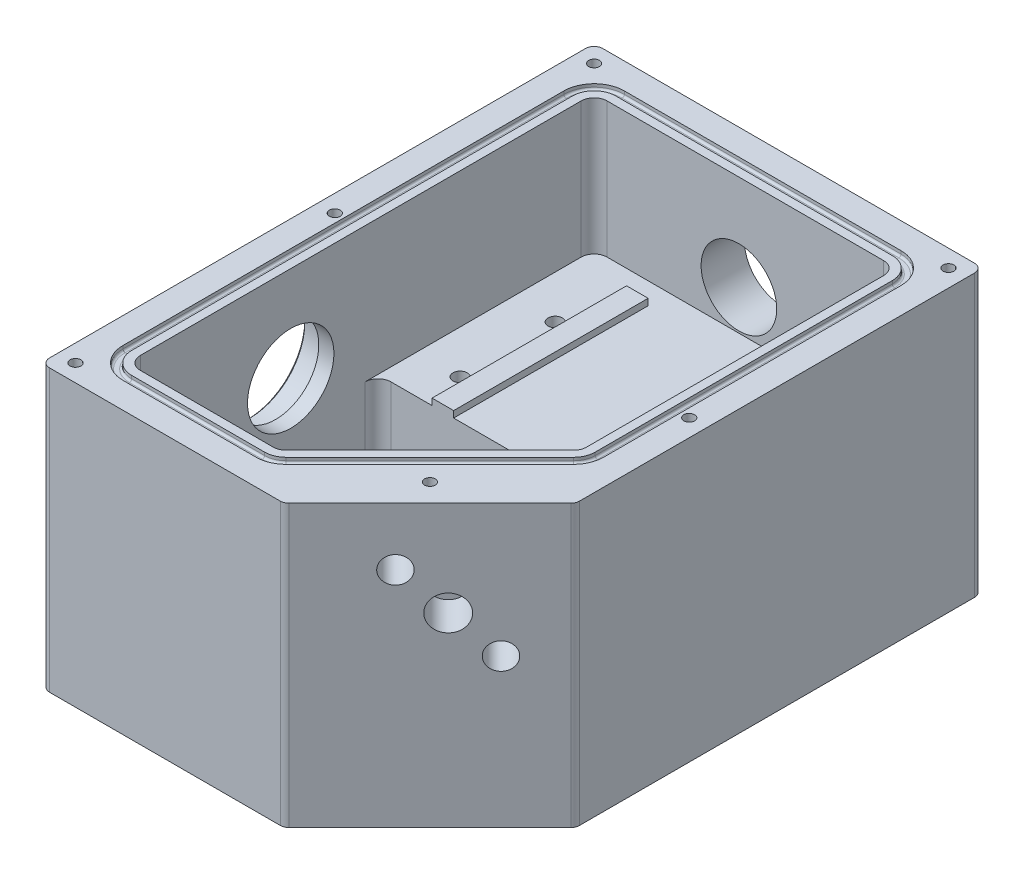
SolidWorks part; units mm, degrees
ref_plane "Front Plane" through (0, 0, 0) normal (0, 0, 1) x (1, 0, 0)
ref_plane "Top Plane" through (0, 0, 0) normal (0, 1, 0) x (1, 0, 0)
ref_plane "Right Plane" through (0, 0, 0) normal (1, 0, 0) x (0, 0, -1)
sketch "Sketch1" plane through (0, 0, 0) normal (0, 1, 0) x (1, 0, 0)
  line L1 (-45, -59) -> (45, -59)
  line L2 (-45, -59) -> (-45, 59)
  line L3 (-45, 59) -> (45, 59)
  line L4 (45, -59) -> (45, 59)
  line L5 (-45, -59) -> (45, 59) construction
  line L6 (-45, 59) -> (45, -59) construction
  point P0 (0, 0)
  dimension "D1" = 118
  dimension "D2" = 90
extrude "Boss-Extrude1" add sketch "Sketch1" along normal blind 15
sketch "Sketch3" plane through (0, 15, 0) normal (0, 1, 0) x (1, 0, 0)
  line L0 (45, -59) -> (45, 59) construction
  line L1 (-45, 59) -> (45, 59)
  line L2 (-45, 59) -> (-45, 9)
  line L3 (-45, 9) -> (45, 9)
  line L4 (45, 59) -> (45, 9)
  dimension "D1" = 50
extrude "Boss-Extrude3" add sketch "Sketch3" along normal blind 18.7
sketch "Sketch45" plane through (0, 0, -9) normal (0, 0, 1) x (1, 0, 0)
  line L1 (-22.5, 35.2) -> (-17.5, 35.2)
  line L2 (-22.5, 35.2) -> (-22.5, 33.7)
  line L3 (-22.5, 33.7) -> (-17.5, 33.7)
  line L4 (-17.5, 35.2) -> (-17.5, 33.7)
extrude "Boss-Extrude10" add sketch "Sketch45" against normal blind 45
sketch "Sketch6" plane through (0, 33.7, 0) normal (0, 1, 0) x (1, 0, 0)
  line L1 (-25, 18) -> (25, 18) construction
  line L2 (-25, 18) -> (-25, 40) construction
  line L3 (-25, 40) -> (25, 40) construction
  line L4 (25, 18) -> (25, 40) construction
  line L5 (-25, 18) -> (25, 40) construction
  line L6 (-25, 40) -> (25, 18) construction
  line L7 (-45, 9) -> (-22.5, 9) construction
  line L8 (-25, 22.18) -> (-25, 35.82) construction
  point P0 (0, 29)
  dimension "D1" = 22
  dimension "D3" = 20
hole_wizard "M4 Tapped Hole1" positions "3DSketch3" profile "Sketch7" tap size "M4" standard "ISO"
sketch3d "3DSketch3"
  point P0 (-25, 33.7, -40)
  point P3 (25, 33.7, -40)
  point P6 (25, 33.7, -18)
  point P9 (-25, 33.7, -18)
sketch "Sketch7" plane through (-25, 33.7, -40) normal (1, 0, 0) x (0, 0, 1)
  line L0 (0, 0) -> (0, 7.5954)
  line L1 (0, 7.5954) -> (1.65, 6.604)
  line L2 (1.65, 6.604) -> (1.65, 0)
  line L5 (1.65, 0) -> (0, 0)
  line L10 (0, 7.5954) -> (-1.65, 6.604) construction
  line L11 (0, -6.35) -> (0, 107.95) construction
  dimension "Tap Drill Dia." = 3.3
  dimension "Tap Drill Depth" = 6.604
  dimension "Drill Angle" = 118
cosmetic thread "Hole Thread1" parameters "D1"=3.048, "D2"=4
cosmetic thread "Hole Thread2" parameters "D1"=3.048, "D2"=4
cosmetic thread "Hole Thread3" parameters "D1"=3.048, "D2"=4
cosmetic thread "Hole Thread4" parameters "D1"=3.048, "D2"=4
sketch "Sketch9" plane through (0, 15, 0) normal (0, 1, 0) x (1, 0, 0)
  line L0 (45, -4) -> (-10, -59)
  line L1 (45, -59) -> (45, 9) construction
  line L2 (-45, -59) -> (45, -59) construction
  line L3 (-10, -59) -> (45, -59)
  line L4 (45, -59) -> (45, -4)
  dimension "D1" = 45
  dimension "D2" = 55
extrude "Boss-Extrude5" add sketch "Sketch9" along normal blind 50
sketch "Sketch10" plane through (0, 65, 0) normal (0, 1, 0) x (1, 0, 0)
  line L0 (45, -25.2132) -> (11.2132, -59)
  line L1 (45, -59) -> (45, -4) construction
  line L2 (-10, -59) -> (45, -59) construction
  line L3 (45, -4) -> (-10, -59) construction
  line L4 (11.2132, -59) -> (45, -59)
  line L5 (45, -59) -> (45, -25.2132)
  dimension "D1" = 15
extrude "Cut-Extrude2" cut sketch "Sketch10" against normal through all
ref_plane "Plane8" through (-7, 0, 7) normal (-0.7071, 0, 0.7071) x (0.7071, 0, 0.7071)
sketch "Sketch19" plane through (45, 0, 0) normal (1, 0, 0) x (0, 0, -1)
  line L1 (-25.2132, 65) -> (59, 65)
  line L2 (-25.2132, 65) -> (-25.2132, 0)
  line L3 (-25.2132, 0) -> (59, 0)
  line L4 (59, 65) -> (59, 0)
extrude "Boss-Extrude6" add sketch "Sketch19" against normal blind 10
sketch "Sketch20" plane through (0, 0, 59) normal (0, 0, 1) x (1, 0, 0)
  line L1 (11.2132, 65) -> (-45, 65)
  line L2 (11.2132, 65) -> (11.2132, 0)
  line L3 (11.2132, 0) -> (-45, 0)
  line L4 (-45, 65) -> (-45, 0)
extrude "Boss-Extrude7" add sketch "Sketch20" against normal blind 10
sketch "Sketch21" plane through (-45, 0, 0) normal (-1, 0, 0) x (0, 0, 1)
  line L1 (-59, 0) -> (59, 0)
  line L2 (-59, 0) -> (-59, 65)
  line L3 (-59, 65) -> (59, 65)
  line L4 (59, 0) -> (59, 65)
extrude "Boss-Extrude8" add sketch "Sketch21" against normal blind 10
sketch "Sketch22" plane through (0, 0, -59) normal (0, 0, -1) x (-1, 0, 0)
  line L1 (-45, 0) -> (45, 0)
  line L2 (-45, 0) -> (-45, 65)
  line L3 (-45, 65) -> (45, 65)
  line L4 (45, 0) -> (45, 65)
extrude "Boss-Extrude9" add sketch "Sketch22" along normal blind 10
fillet "Fillet1" radius 3 5 edges at (0, 40, 49) (35, 40, 14) (-35, 40, 49)
fillet "Fillet3" radius 3 2 edges at (35, 24.35, -9) (-35, 24.35, -9)
fillet "Fillet5" radius 2 5 edges at (-45, 32.5, 59) (11.2132, 32.5, 59) (-45, 32.5, -69) (45, 32.5, -69) (45, 32.5, 25.2132)
hole_wizard "CBORE for M5 Hex Head Bolt1" positions "3DSketch11" profile "Sketch49" counterbore size "M5" standard "ISO" end condition up to next
sketch3d "3DSketch11"
  line L0 (1.85, 43, 11.1991) -> (-68.0499, 43, 11.1991) construction
  point P0 (-45, 43, 11.1991)
sketch "Sketch49" plane through (-45, 43, 11.1991) normal (0, 1, 0) x (0, 0, 1)
  line L0 (0, 0) -> (0, 10)
  line L1 (0, 10) -> (10, 10)
  line L3 (10, 10) -> (10, 6.5)
  line L4 (10, 6.5) -> (12.75, 6.5)
  line L5 (12.75, 6.5) -> (12.75, 0)
  line L7 (12.75, 0) -> (0, 0)
  line L11 (0, -6.35) -> (0, 107.95) construction
  dimension "Thru Hole Dia." = 20
  dimension "Thru Hole Depth" = 10
  dimension "C'Bore Dia." = 25.5
  dimension "C'Bore Depth" = 6.5
chamfer "Chamfer1" distance 0.5 angle 45 1 edges at (-45, 43, 23.9491)
sketch "Sketch52" plane through (0, 65, 0) normal (0, 1, 0) x (1, 0, 0)
  line L16 (3, -50.2426) -> (36.2426, -17)
  line L17 (-32, -52) -> (-1.2426, -52)
  line L18 (-38, 56) -> (-38, -46)
  line L19 (32, 62) -> (-32, 62)
  line L20 (38, -12.7574) -> (38, 56)
  line L21 (3, -50.2426) -> (36.2426, -17)
  line L22 (-32, -52) -> (-1.2426, -52)
  line L23 (-38, 56) -> (-38, -46)
  line L24 (32, 62) -> (-32, 62)
  line L25 (38, -12.7574) -> (38, 56)
  arc A15 (-1.2426, -52) -> (3, -50.2426) centre (-1.2426, -46) ccw
  arc A16 (-38, -46) -> (-32, -52) centre (-32, -46) ccw
  arc A17 (-32, 62) -> (-38, 56) centre (-32, 56) ccw
  arc A18 (38, 56) -> (32, 62) centre (32, 56) ccw
  arc A19 (36.2426, -17) -> (38, -12.7574) centre (32, -12.7574) ccw
  arc A20 (-1.2426, -52) -> (3, -50.2426) centre (-1.2426, -46) ccw
  arc A21 (-38, -46) -> (-32, -52) centre (-32, -46) ccw
  arc A22 (-32, 62) -> (-38, 56) centre (-32, 56) ccw
  arc A23 (38, 56) -> (32, 62) centre (32, 56) ccw
  arc A24 (36.2426, -17) -> (38, -12.7574) centre (32, -12.7574) ccw
  dimension "D1" = 3
ref_plane "Plane29" through (0, 0, -56) normal (0, 0, -1) x (-1, 0, 0)
sketch "Sketch53" plane through (0, 0, -56) normal (0, 0, -1) x (-1, 0, 0)
  line L1 (-38.5, 63.8) -> (-37.5, 63.8)
  line L2 (-39, 64.3) -> (-39, 66.2)
  line L3 (-39, 66.2) -> (-37, 66.2)
  line L4 (-37, 64.3) -> (-37, 66.2)
  line L5 (-39, 63.8) -> (-37, 66.2) construction
  line L6 (-39, 66.2) -> (-37, 63.8) construction
  arc A0 (-37, 64.3) -> (-37.5, 63.8) centre (-37.5, 64.3) cw
  arc A1 (-38.5, 63.8) -> (-39, 64.3) centre (-38.5, 64.3) cw
  point P0 (-38, 65)
  dimension "D3" = 0.5
  dimension "D1" = 2
  dimension "D2" = 1.2
sweep "Cut-Sweep5" cut profiles "Sketch53" path "Sketch52"
mirror "Mirror2" about plane through (0, 0, 0) normal (1, 0, 0) of "Boss-Extrude10"
hole_wizard "M20 Tapped Hole1" positions "3DSketch9" profile "Sketch46" tap size "M20" standard "ISO" end condition up to next
sketch3d "3DSketch9"
  line L0 (-1.5, 42.9, -29.8) -> (-1.5, 42.9, -80.5766) construction
  point P0 (-1.5, 42.9, -69)
sketch "Sketch46" plane through (-1.5, 42.9, -69) normal (1, 0, 0) x (0, 1, 0)
  line L0 (0, 0) -> (0, 10)
  line L1 (0, 10) -> (8.75, 10)
  line L2 (8.75, 10) -> (8.75, 0)
  line L5 (8.75, 0) -> (0, 0)
  line L11 (0, -6.35) -> (0, 107.95) construction
  dimension "Thru Tap Drill Dia." = 17.5
  dimension "Thru Tap Drill Depth" = 10
cosmetic thread "Hole Thread19" parameters "D2"=20
sketch "Sketch47" plane through (0, 65, 0) normal (0, 1, 0) x (1, 0, 0)
  line L0 (-45, 5) -> (45, 5) construction
  line L1 (-45, 67) -> (-45, -57) construction
  line L2 (45, -24.3848) -> (45, 67) construction
  line L3 (0, 69) -> (0, -59) construction
  line L4 (-43, 69) -> (43, 69) construction
  line L5 (-43, -59) -> (10.3848, -59) construction
  line L6 (28.1066, -42.1066) -> (17.5, -31.5) construction
  line L7 (44.4142, -25.799) -> (11.799, -58.4142) construction
  line L8 (34.1213, -14.8787) -> (0.8787, -48.1213) construction
  point P0 (-41, 65)
  point P1 (41, 65)
  point P2 (41, 5)
  point P3 (-41, 5)
  point P4 (-41, -55)
  point P6 (23.864, -37.864)
  dimension "D1" = 4
  dimension "D2" = 4
  dimension "D3" = 4
  dimension "D4" = 6
  dimension "D5" = 4
hole_wizard "M3 Tapped Hole1" positions "3DSketch10" profile "Sketch48" tap size "M3" standard "ISO"
sketch3d "3DSketch10"
  point P0 (-41, 65, -65)
  point P3 (41, 65, -65)
  point P6 (41, 65, -5)
  point P9 (-41, 65, -5)
  point P12 (-41, 65, 55)
  point P18 (23.864, 65, 37.864)
sketch "Sketch48" plane through (-41, 65, -65) normal (1, 0, 0) x (0, 0, 1)
  line L0 (0, 0) -> (0, 9.2511)
  line L1 (0, 9.2511) -> (1.25, 8.5)
  line L2 (1.25, 8.5) -> (1.25, 0)
  line L5 (1.25, 0) -> (0, 0)
  line L10 (0, 9.2511) -> (-1.25, 8.5) construction
  line L11 (0, -6.35) -> (0, 107.95) construction
  dimension "Tap Drill Dia." = 2.5
  dimension "Tap Drill Depth" = 8.5
  dimension "Drill Angle" = 118
cosmetic thread "Hole Thread21" parameters "D1"=6, "D2"=3
cosmetic thread "Hole Thread23" parameters "D1"=6, "D2"=3
cosmetic thread "Hole Thread24" parameters "D1"=6, "D2"=3
cosmetic thread "Hole Thread25" parameters "D1"=6, "D2"=3
cosmetic thread "Hole Thread26" parameters "D1"=6, "D2"=3
cosmetic thread "Hole Thread27" parameters "D1"=6, "D2"=3
hole_wizard "Ø3.0 (3) Diameter Hole1" positions "3DSketch12" profile "Sketch56" hole size "Ø3.0" standard "ISO"
sketch3d "3DSketch12"
  line L0 (-23.15, 10, -7.5) -> (-23.15, 50, -7.5) construction
  line L1 (26.85, 50, -7.5) -> (26.85, 10, -7.5) construction
  point P0 (-23.15, 15, -7.5)
  point P2 (26.85, 15, -7.5)
sketch "Sketch56" plane through (-23.15, 15, -7.5) normal (1, 0, 0) x (0, 0, 1)
  line L0 (0, 0) -> (0, 5.9003)
  line L1 (0, 5.9003) -> (1.5, 4.999)
  line L2 (1.5, 4.999) -> (1.5, 0)
  line L5 (1.5, 0) -> (0, 0)
  line L10 (0, 5.9003) -> (-1.5, 4.999) construction
  line L11 (0, -6.35) -> (0, 107.95) construction
  dimension "Hole Dia." = 3
  dimension "Hole Depth" = 4.999
  dimension "Drill Angle" = 118
sketch "Sketch55" plane through (0, 15, 0) normal (0, 1, 0) x (1, 0, 0)
  line L4 (26.85, 7.5) -> (-23.15, 7.5)
  line L5 (26.85, -7.5) -> (26.85, 7.5)
  line L6 (-18.15, -12.5) -> (21.85, -12.5)
  line L7 (-23.15, 7.5) -> (-23.15, -7.5)
  line L8 (26.85, 7.5) -> (-23.15, 7.5)
  line L9 (26.85, -7.5) -> (26.85, 7.5)
  line L10 (-18.15, -12.5) -> (21.85, -12.5)
  line L11 (-23.15, 7.5) -> (-23.15, -7.5)
  arc A2 (21.85, -12.5) -> (26.85, -7.5) centre (21.85, -7.5) ccw
  arc A3 (-23.15, -7.5) -> (-18.15, -12.5) centre (-18.15, -7.5) ccw
  arc A4 (21.85, -12.5) -> (26.85, -7.5) centre (21.85, -7.5) ccw
  arc A5 (-23.15, -7.5) -> (-18.15, -12.5) centre (-18.15, -7.5) ccw
  dimension "D1" = 0
extrude "Cut-Extrude8" cut sketch "Sketch55" against normal up to surface (5 mm away)
ref_plane "Plane30" through (-4.8787, 0, 4.8787) normal (-0.7071, 0, 0.7071) x (0.7071, 0, 0.7071)
sketch "Sketch57" plane through (35.1066, 0, 35.1066) normal (0.7071, 0, 0.7071) x (0.7071, 0, -0.7071)
  circle A0 centre (-15.5355, 51.636) radius 3.067 construction
  circle A1 centre (1.7365, 34.364) radius 3.0671 construction
  circle A2 centre (-15.5355, 51.636) radius 3.067
  circle A3 centre (1.7365, 34.364) radius 3.067
extrude "KMSS_brass_pin_locator" cut sketch "Sketch57" against normal up to next
hole_wizard "CBORE for M4 Hex Socket Head Cap Screw1" positions "3DSketch13" profile "Sketch59" counterbore size "M4" standard "ISO" end condition up to next
sketch3d "3DSketch13"
  point P0 (30.2279, 43, 39.9853)
sketch "Sketch59" plane through (30.2279, 43, 39.9853) normal (0, 1, 0) x (0.7071, 0, -0.7071)
  line L0 (0, 0) -> (0, 15)
  line L1 (0, 15) -> (2.15, 15)
  line L3 (2.15, 15) -> (2.15, 9.4)
  line L4 (2.15, 9.4) -> (4, 9.4)
  line L5 (4, 9.4) -> (4, 0)
  line L7 (4, 0) -> (0, 0)
  line L11 (0, -6.35) -> (0, 107.95) construction
  dimension "Thru Hole Dia." = 4.3
  dimension "Thru Hole Depth" = 15
  dimension "C'Bore Dia." = 8
  dimension "C'Bore Depth" = 9.4
